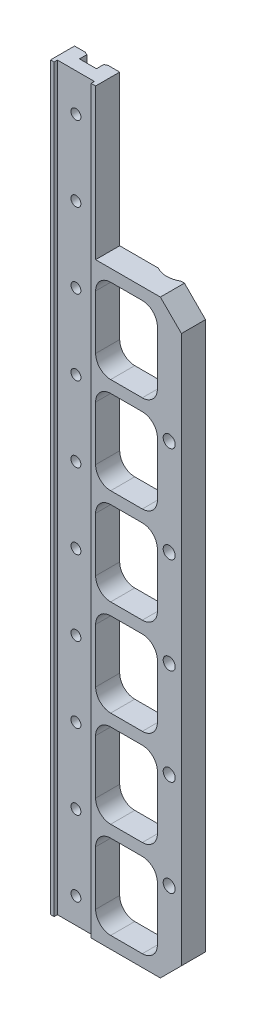
SolidWorks part; units mm, degrees
ref_plane "Plan de face" through (0, 0, 0) normal (0, 0, 1) x (1, 0, 0)
ref_plane "Plan de dessus" through (0, 0, 0) normal (0, 1, 0) x (1, 0, 0)
ref_plane "Plan de droite" through (0, 0, 0) normal (1, 0, 0) x (0, 0, -1)
sketch "Esquisse1" plane through (0, 0, 0) normal (0, 1, 0) x (1, 0, 0)
  line L69 (0, -8.1) -> (0, -0.1)
  line L71 (0, 0) -> (-8.0914, 0) construction
  line L216 (-43.5164, -0.1) -> (-43.5164, -8.1)
  line L218 (-43.5164, -8.1) -> (-42.3164, -8.1)
  line L220 (-42.3164, -8.1) -> (-42.3164, -7)
  line L222 (-42.3164, -7) -> (-30.0164, -7)
  line L317 (-30.0164, -7) -> (-30.0164, -8.1)
  line L319 (-30.0164, -8.1) -> (0, -8.1)
  line L320 (-38.5414, 1.45) -> (-39.9914, 0) construction
  line L321 (-33.7914, 1.45) -> (-38.5414, 1.45) construction
  line L322 (-32.3414, 0) -> (-33.7914, 1.45) construction
  line L323 (-32.3414, 0) -> (-15.7414, 0) construction
  line L324 (-15.7414, 0) -> (-14.2914, 1.45) construction
  line L325 (-14.2914, 1.45) -> (-9.5414, 1.45) construction
  line L326 (-9.5414, 1.45) -> (-8.0914, 0) construction
  line L327 (-38.5414, 1.45) -> (-39.9914, 0) construction
  line L328 (-33.7914, 1.45) -> (-38.5414, 1.45) construction
  line L329 (-32.3414, 0) -> (-33.7914, 1.45) construction
  line L330 (-32.3414, 0) -> (-15.7414, 0) construction
  line L331 (-15.7414, 0) -> (-14.2914, 1.45) construction
  line L332 (-14.2914, 1.45) -> (-9.5414, 1.45) construction
  line L333 (-9.5414, 1.45) -> (-8.0914, 0) construction
  line L334 (0, -0.1) -> (-8.1328, -0.1)
  line L338 (-32.3828, -0.1) -> (-15.7, -0.1)
  line L342 (0, 0) -> (-8, 0) construction
  line L343 (-9.5828, 1.35) -> (-8.1621, -0.0707) construction
  line L344 (0, -0.1) -> (-8, -0.1) construction
  line L345 (-47.0414, 0) -> (-39.9914, 0) construction
  line L346 (-47.0414, 0) -> (-39.9914, 0) construction
  line L347 (-43.5164, -0.1) -> (-39.95, -0.1)
  line L348 (-38.5, 1.35) -> (-39.9207, -0.0707) construction
  line L349 (-47.0414, -0.1) -> (-39.9914, -0.1) construction
  line L350 (-15.7, -0.1) -> (-14.25, 1.35) construction
  line L351 (-14.25, 1.35) -> (-9.5828, 1.35) construction
  line L352 (-32.3828, -0.1) -> (-33.8328, 1.35) construction
  line L353 (-33.8328, 1.35) -> (-38.5, 1.35) construction
  line L354 (-36.1664, -1.1) -> (-11.9164, -1.1) construction
  line L355 (-38.4707, 1.3793) -> (-39.95, -0.1) construction
  line L356 (-38.4707, 1.3793) -> (-39.9207, -0.0707) construction
  line L357 (-9.6121, 1.3793) -> (-8.1328, -0.1) construction
  line L358 (-9.6121, 1.3793) -> (-8.1621, -0.0707) construction
  line L359 (-36.1664, -7) -> (-36.1664, -1.1) construction
  arc A1 (-8.1328, -0.1) -> (-15.7, -0.1) centre (-11.9164, 6.5577) cw
  arc A2 (-32.3828, -0.1) -> (-39.95, -0.1) centre (-36.1664, 6.5577) cw
  point P30 (-41.5, -8)
  point P32 (0, 0)
  point P33 (-40.5, -6)
  point P38 (0, 0)
  point P41 (-28.2, -8)
  point P42 (0, 0)
  point P43 (-34.35, -6)
  point P44 (-41.5, 0)
  point P45 (0, 0)
  point P46 (-34.35, -6)
  point P47 (-36.8722, -5.1009)
  point P48 (0, 0)
  point P49 (-41.9083, -6)
  point P50 (-36.8722, -4.4618)
  point P51 (-46.5865, -6)
  point P52 (-40.4365, -6)
  point P53 (0, 0)
  dimension "D1" = 12.3
  dimension "D2" = 1.2
  dimension "D4" = 8
  dimension "D5" = 6.9
  dimension "D7" = 1
  dimension "D3" = 0.1
  dimension "D6" = 0.1
  dimension "D8" = 0.1
  dimension "D9" = 0.1
extrude "Boss.-Extru.1" add sketch "Esquisse1" along normal blind 246
sketch "Esquisse2" plane through (0, 0, 0.1) normal (0, 0, -1) x (-1, 0, 0)
  line L1 (13, 4) -> (23.5164, 4)
  line L2 (8, 9) -> (8, 27)
  line L3 (13, 32) -> (23.5164, 32)
  line L4 (28.5164, 9) -> (28.5164, 27)
  line L7 (15.7, 0) -> (32.3828, 0) construction
  line L8 (43.5164, 246) -> (43.5164, 0) construction
  line L9 (0, 246) -> (0, 0) construction
  arc A0 (23.5164, 32) -> (28.5164, 27) centre (23.5164, 27) cw
  arc A1 (23.5164, 4) -> (28.5164, 9) centre (23.5164, 9) ccw
  arc A2 (13, 4) -> (8, 9) centre (13, 9) cw
  arc A3 (8, 27) -> (13, 32) centre (13, 27) cw
  dimension "D3" = 5
  dimension "D1" = 8
  dimension "D2" = 15
  dimension "D4" = 28
  dimension "D5" = 4
extrude "Enlèv. mat.-Extru.1" cut sketch "Esquisse2" against normal through all
pattern_linear "Répétition linéaire1" count 9 spacing 32 along (0, 1, 0) of "Enlèv. mat.-Extru.1"
sketch "Esquisse3" plane through (0, 0, 7) normal (0, 0, 1) x (1, 0, 0)
  line L0 (-36.1664, 0) -> (-36.1664, 8.5) construction
  line L1 (-42.3164, 0) -> (-30.0164, 0) construction
  circle A1 centre (-36.1664, 8.5) radius 1.65
  dimension "D1" = 3.3
  dimension "D2" = 8.5
extrude "Enlèv. mat.-Extru.2" cut sketch "Esquisse3" against normal through all
sketch "Esquisse14" plane through (0, 0, 7) normal (0, 0, -1) x (-1, 0, 0)
  line L0 (33.3414, -4) -> (33.3414, 21)
  line L1 (33.3414, 21) -> (38.9914, 21)
  line L2 (38.9914, 21) -> (38.9914, -4)
  line L3 (38.9914, -4) -> (33.3414, -4)
  line L4 (36.1664, 8.5) -> (33.3414, 8.5) construction
  line L5 (36.1664, -4) -> (36.1664, 8.5) construction
  dimension "D1" = 5.65
  dimension "D2" = 12.5
extrude "Enlèv. mat.-Extru.8" cut sketch "Esquisse14" along normal through all from offset 4
pattern_linear "Répétition linéaire4" count 10 spacing 25 along (0, 1, 0) of "Enlèv. mat.-Extru.8", "Enlèv. mat.-Extru.2"
sketch "Esquisse7" plane through (0, 0, 0.1) normal (0, 0, -1) x (-1, 0, 0)
  line L0 (4.0664, 0) -> (4.0664, 28) construction
  line L3 (0, 0) -> (8.1328, 0) construction
  circle A0 centre (4.0664, 28) radius 2
  point P7 (4.0664, 0)
  dimension "D1" = 4
  dimension "D2" = 28
extrude "Enlèv. mat.-Extru.4" cut sketch "Esquisse7" against normal through all
pattern_linear "Répétition linéaire3" count 5 spacing 32 along (0, 1, 0) of "Enlèv. mat.-Extru.4"
sketch "Esquisse12" plane through (0, 0, 8.1) normal (0, 0, 1) x (1, 0, 0)
  line L0 (0, 246) -> (0, 0) construction
  line L1 (0, 196) -> (-28.5164, 196)
  line L2 (0, 196) -> (0, 246)
  line L3 (0, 246) -> (-28.5164, 246)
  line L4 (-28.5164, 196) -> (-28.5164, 246)
  line L5 (-13, 196) -> (-23.5164, 196) construction
  line L6 (-30.0164, 246) -> (-28.5164, 246) construction
  line L9 (-28.5164, 201) -> (-28.5164, 219) construction
extrude "Enlèv. mat.-Extru.6" cut sketch "Esquisse12" against normal through all
chamfer "Chanfrein1" distance 7 angle 45 2 edges at (0, 0, 4.1) (0, 196, 4.1)
chamfer "Chanfrein2" [suppressed] distance 7 angle 45
move or copy body "Corps-Déplacer/Copier2" [suppressed] bodies to move or copy 110
move or copy body "Corps-Déplacer/Copier1" [suppressed] bodies to move or copy 108
equation "\"length\"= 246mm"
equation "\"D1@Boss.-Extru.1\"=\"length\""
